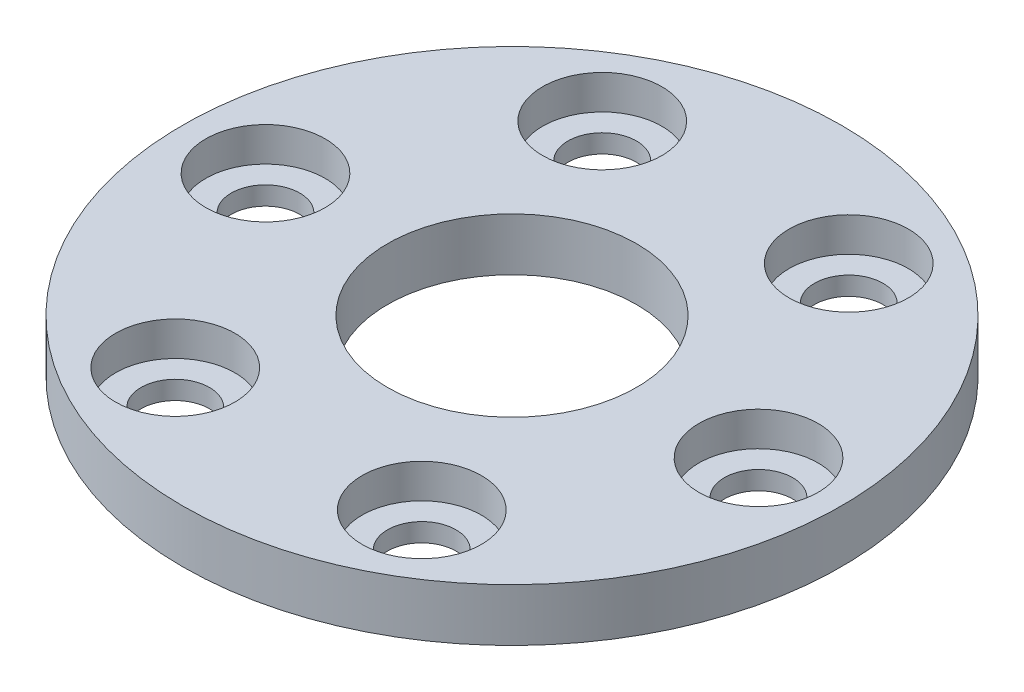
SolidWorks part; units mm, degrees
material "6063-O"
ref_plane "Front Plane" through (0, 0, 0) normal (0, 0, 1) x (1, 0, 0)
ref_plane "Top Plane" through (0, 0, 0) normal (0, 1, 0) x (1, 0, 0)
ref_plane "Right Plane" through (0, 0, 0) normal (1, 0, 0) x (0, 0, -1)
sketch "Sketch1" plane through (0, 0, 0) normal (0, 1, 0) x (1, 0, 0)
  circle A0 centre (0, 0) radius 31.75
  dimension "D1" = 63.5
extrude "Boss-Extrude1" add sketch "Sketch1" along normal blind 5.08
sketch "Sketch2" plane through (0, 5.08, 0) normal (0, 1, 0) x (1, 0, 0)
  line L0 (0, 0) -> (-23.75, 0) construction
  circle A0 centre (0, 0) radius 23.75 construction
  circle A1 centre (-23.75, 0) radius 2.6
  circle A2 centre (-11.875, 20.5681) radius 2.6
  circle A3 centre (11.875, 20.5681) radius 2.6
  circle A4 centre (23.75, 0) radius 2.6
  circle A5 centre (11.875, -20.5681) radius 2.6
  circle A6 centre (-11.875, -20.5681) radius 2.6
  point P17 (0, 0)
  dimension "D1" = 47.5
  dimension "D2" = 5.2
  dimension "D3" = 6
hole_wizard "CBORE for M6 SBHCS1" positions "Sketch3" profile "Sketch4" counterbore size "M6" standard "ANSI Metric" end condition through all
sketch "Sketch3" plane through (0, 5.08, 0) normal (0, 1, 0) x (1, 0, 0)
  point P0 (-23.75, 0)
  point P3 (-11.875, 20.5681)
  point P6 (11.875, 20.5681)
  point P9 (23.75, 0)
  point P12 (11.875, -20.5681)
  point P15 (-11.875, -20.5681)
sketch "Sketch4" plane through (-23.75, 5.08, 0) normal (1, 0, 0) x (0, 0, 1)
  line L0 (0, 0) -> (0, 5.08)
  line L1 (0, 5.08) -> (3.3, 5.08)
  line L3 (3.3, 5.08) -> (3.3, 3.3)
  line L4 (3.3, 3.3) -> (5.75, 3.3)
  line L5 (5.75, 3.3) -> (5.75, 0)
  line L7 (5.75, 0) -> (0, 0)
  line L11 (0, -6.35) -> (0, 107.95) construction
  dimension "Thru Hole Dia." = 6.6
  dimension "Thru Hole Depth" = 5.08
  dimension "C'Bore Dia." = 11.5
  dimension "C'Bore Depth" = 3.3
sketch "Sketch5" plane through (0, 5.08, 0) normal (0, 1, 0) x (1, 0, 0)
  circle A0 centre (0, 0) radius 12
  dimension "D1" = 24
extrude "Cut-Extrude1" cut sketch "Sketch5" against normal through all
